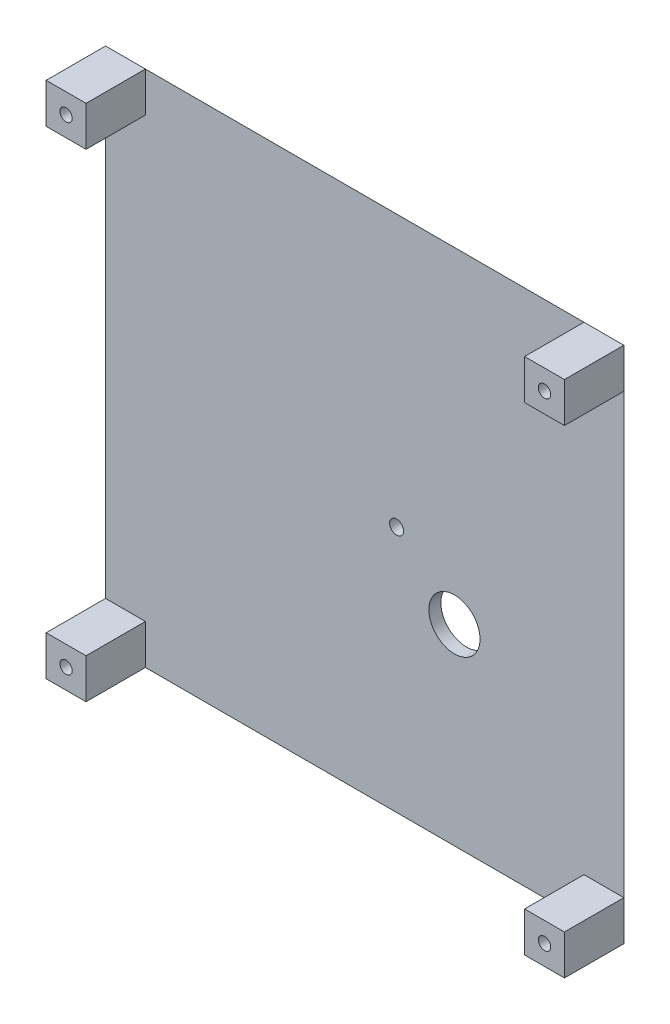
SolidWorks part; units mm, degrees
ref_plane "Plan de face" through (0, 0, 0) normal (0, 0, 1) x (1, 0, 0)
ref_plane "Plan de dessus" through (0, 0, 0) normal (0, 1, 0) x (1, 0, 0)
ref_plane "Plan de droite" through (0, 0, 0) normal (1, 0, 0) x (0, 0, -1)
sketch "Esquisse1" plane through (0, 0, 0) normal (0, 0, 1) x (1, 0, 0)
  line L1 (0, 130) -> (130, 130)
  line L2 (0, 130) -> (0, 0)
  line L3 (0, 0) -> (130, 0)
  line L4 (130, 130) -> (130, 0)
  dimension "D1" = 130
  dimension "D2" = 130
extrude "Boss.-Extru.1" add sketch "Esquisse1" along normal blind 3
chamfer "Chanfrein1" distance 3 angle 45 4 edges at (65, 130, 0) (130, 65, 0) (65, 0, 0) (0, 65, 0)
sketch "Esquisse2" plane through (0, 0, 3) normal (0, 0, 1) x (1, 0, 0)
  line L1 (0, 130) -> (10, 130)
  line L2 (0, 130) -> (0, 120)
  line L3 (0, 120) -> (10, 120)
  line L4 (10, 130) -> (10, 120)
  line L5 (130, 130) -> (120, 130)
  line L6 (130, 130) -> (130, 120)
  line L7 (130, 120) -> (120, 120)
  line L8 (120, 130) -> (120, 120)
  line L9 (130, 0) -> (120, 0)
  line L10 (130, 0) -> (130, 10)
  line L11 (130, 10) -> (120, 10)
  line L12 (120, 0) -> (120, 10)
  line L13 (0, 0) -> (10, 0)
  line L14 (0, 0) -> (0, 10)
  line L15 (0, 10) -> (10, 10)
  line L16 (10, 0) -> (10, 10)
  circle A0 centre (5, 125) radius 1.55
  circle A1 centre (125, 125) radius 1.55
  circle A2 centre (5, 5) radius 1.55
  circle A3 centre (125, 5) radius 1.55
  dimension "D9" = 3.1
  dimension "D10" = 3.1
  dimension "D11" = 3.1
  dimension "D12" = 3.1
  dimension "D1" = 10
  dimension "D2" = 10
  dimension "D3" = 10
  dimension "D4" = 10
  dimension "D5" = 10
  dimension "D6" = 10
  dimension "D7" = 10
  dimension "D8" = 10
extrude "Boss.-Extru.2" add sketch "Esquisse2" along normal blind 14.9
sketch "Esquisse3" plane through (0, 0, 3) normal (0, 0, 1) x (1, 0, 0)
  line L0 (130, 10) -> (130, 120) construction
  line L1 (10, 0) -> (120, 0) construction
  circle A0 centre (87.5137, 48.1148) radius 6.4153
  circle A1 centre (73, 62) radius 1.75
  dimension "D1" = 3.5
  dimension "D2" = 57
  dimension "D3" = 62
extrude "Enlèv. mat.-Extru.1" cut sketch "Esquisse3" against normal blind 14.9
